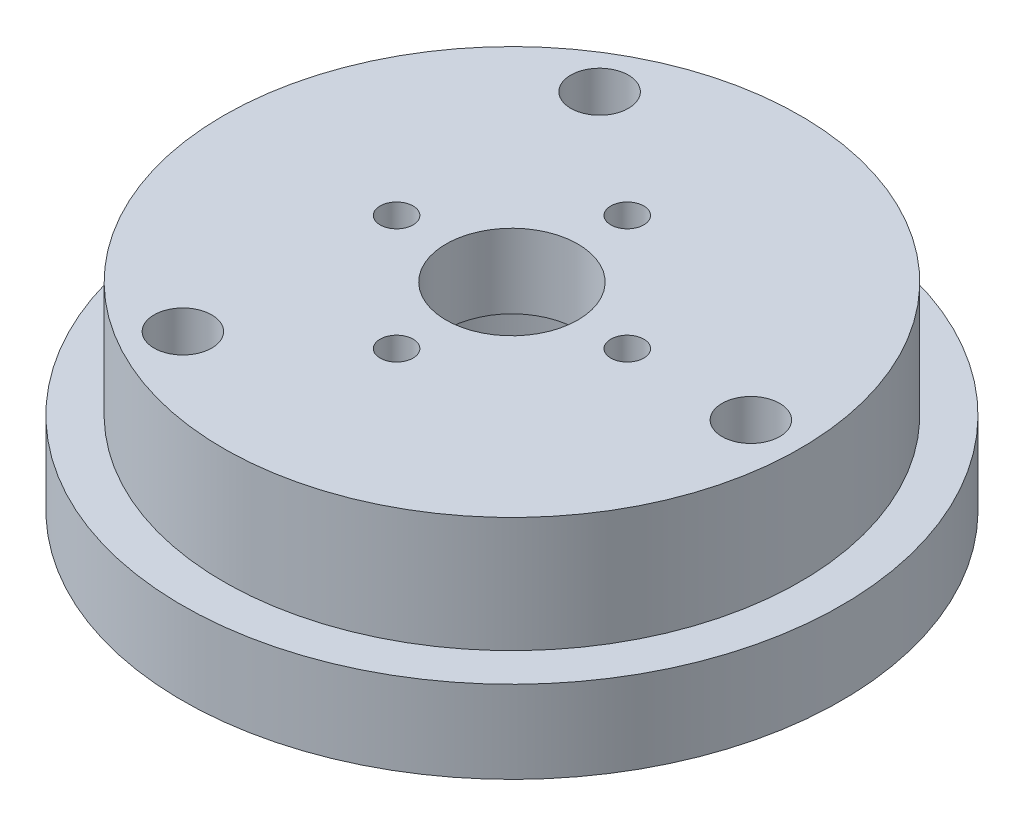
SolidWorks part; units mm, degrees
ref_plane "Front Plane" through (0, 0, 0) normal (0, 0, 1) x (1, 0, 0)
ref_plane "Top Plane" through (0, 0, 0) normal (0, 1, 0) x (1, 0, 0)
ref_plane "Right Plane" through (0, 0, 0) normal (1, 0, 0) x (0, 0, -1)
sketch "Sketch1" plane through (0, 0, 0) normal (0, 0, 1) x (1, 0, 0)
  line L0 (0, 0) -> (-20, 0)
  line L1 (-20, 0) -> (-20, 5)
  line L2 (-20, 5) -> (-17.5, 5)
  line L3 (-17.5, 5) -> (-17.5, 12)
  line L4 (-17.5, 12) -> (0, 12)
  line L5 (0, 12) -> (0, 0)
  dimension "D1" = 20
  dimension "D2" = 5
  dimension "D3" = 12
  dimension "D4" = 17.5
revolve "Revolve2" add sketch "Sketch1" angle 360 about L5 region at (-9.3118, 5.8034, 0)
sketch "Sketch2" plane through (0, 0, 0) normal (0, -1, 0) x (1, 0, 0)
  circle A0 centre (0, 0) radius 10
  circle A1 centre (14.5, 0) radius 1.75
  circle A2 centre (-7.3406, -12.6609) radius 1.75
  circle A3 centre (-7.385, 12.584) radius 1.75
  circle A4 centre (0, 0) radius 4
  circle A5 centre (7, 0) radius 1
  circle A6 centre (0, -7) radius 1
  circle A7 centre (-7, 0) radius 1
  circle A8 centre (0, 7) radius 1
  point P11 (-0.0752, -0.0256)
  point P22 (0, 0)
  dimension "D1" = 20
  dimension "D3" = 3.5
  dimension "D6" = 8
  dimension "D7" = 2
  dimension "D2" = 14.5
  dimension "D8" = 7
  dimension "D4" = 3
extrude "Cut-Extrude5" cut sketch "Sketch2" against normal through all contours A2 | A1 | A3 | A4 | A8 | A7 | A5 | A6 region at (14.5, 0, 0) region at (-7.3406, 0, -12.6609) region at (-7.385, 0, 12.584) region at (0, 0, 0)
sketch "Sketch8" plane through (0, 0, 0) normal (0, -1, 0) x (1, 0, 0)
extrude "Cut-Extrude6" cut sketch "Sketch2<7>" against normal blind 7.5 contours A0
sketch "Sketch2<7>" plane through (0, 0, 0) normal (0, -1, 0) x (1, 0, 0) same geometry as "Sketch2"
sketch "Sketch13" plane through (0, 7.5, 0) normal (0, -1, 0) x (1, 0, 0)
